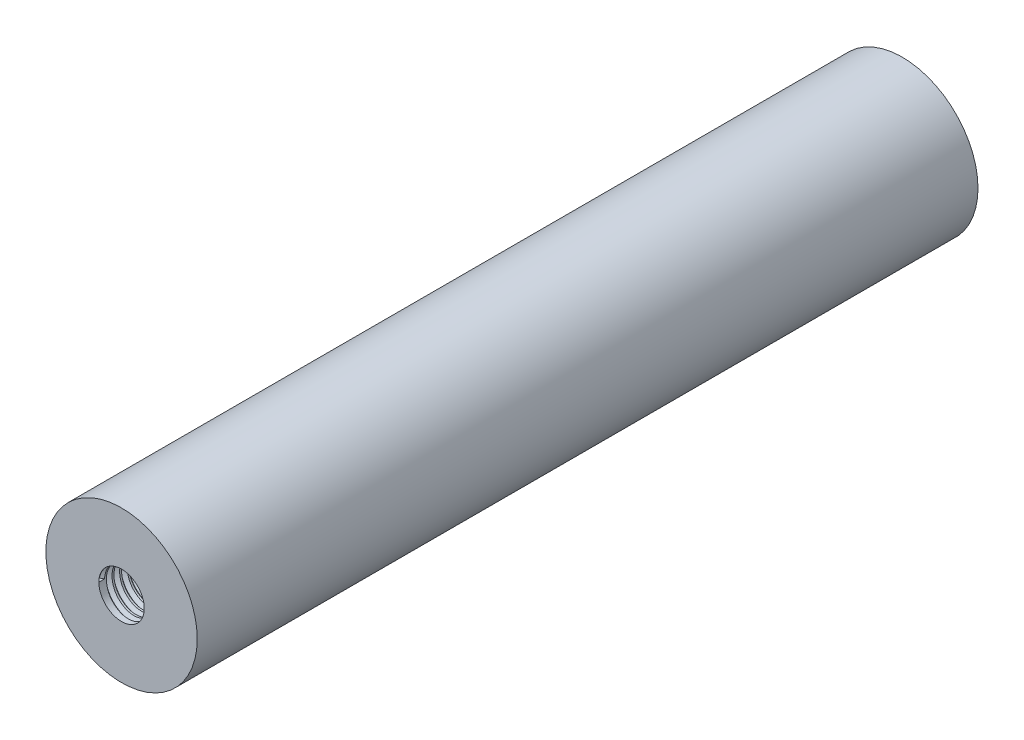
SolidWorks part; units mm, degrees
ref_plane "Front Plane" through (0, 0, 0) normal (0, 0, 1) x (1, 0, 0)
ref_plane "Top Plane" through (0, 0, 0) normal (0, 1, 0) x (1, 0, 0)
ref_plane "Right Plane" through (0, 0, 0) normal (1, 0, 0) x (0, 0, -1)
sketch "Sketch1" plane through (0, 0, 0) normal (0, 0, 1) x (1, 0, 0)
  circle A0 centre (0, 0) radius 10
  dimension "D1" = 20
extrude "Boss-Extrude1" add sketch "Sketch1" along normal mid plane 118.29
sketch "Sketch5" plane through (0, 0, 0) normal (0, 0, 1) x (1, 0, 0)
  line L1 (30.8492, -37.2988) -> (-30.8492, -37.2988)
  line L2 (30.8492, -37.2988) -> (30.8492, 37.2988)
  line L3 (30.8492, 37.2988) -> (-30.8492, 37.2988)
  line L4 (-30.8492, -37.2988) -> (-30.8492, 37.2988)
  line L5 (30.8492, -37.2988) -> (-30.8492, 37.2988) construction
  line L6 (30.8492, 37.2988) -> (-30.8492, -37.2988) construction
  point P0 (0, 0)
extrude "Cut-Extrude2" cut sketch "Sketch5" along normal blind 112 from offset 44
sketch "Sketch6" plane through (0, 0, 44) normal (0, 0, 1) x (1, 0, 0)
  circle A0 centre (0, 0) radius 3
  dimension "D1" = 6
extrude "Cut-Extrude3" cut sketch "Sketch6" against normal blind 10
thread "Thread1" pitch 1 method cut profile "Thread Profile1" start angle 0, offset 0, length 0, pitch 1, diameter 6
ref_plane "Plane1" through (-3, 0, 44) normal (0, -1, 0) x (-1, 0, 0)
sketch "Thread Profile1" plane through (-3, 0, 44) normal (0, -1, 0) x (-1, 0, 0)
  line L0 (0, 0) -> (0, 1) construction
  line L1 (0, 0) -> (0.5413, 0.3125)
  line L2 (0.5413, 0.3125) -> (0.5413, 0.4375)
  line L3 (0.5413, 0.4375) -> (0, 0.75)
  line L4 (0.5413, 0.375) -> (0, 0.375) construction
  line L11 (0, 0) -> (0, 0.75)
  point P2 (0, 0)
  dimension "Pitch" = 1
  dimension "Profile_Angle" = 60
  dimension "Profile_Land" = 0.125
  dimension "Profile_Height" = 0.5413
sketch "Sketch8" plane through (0, 0, -59.145) normal (0, 0, -1) x (-1, 0, 0)
  circle A0 centre (0, 0) radius 3
  dimension "D1" = 6
extrude "Cut-Extrude4" cut sketch "Sketch8" against normal blind 10
thread "Thread2" pitch 1 method cut profile "Thread Profile2" start angle 0, offset 0, length 0, pitch 1, diameter 6
ref_plane "Plane2" through (3, 0, -59.145) normal (0, -1, 0) x (1, 0, 0)
sketch "Thread Profile2" plane through (3, 0, -59.145) normal (0, -1, 0) x (1, 0, 0)
  line L0 (0, 0) -> (0, 1) construction
  line L1 (0, 0) -> (0.5413, 0.3125)
  line L2 (0.5413, 0.3125) -> (0.5413, 0.4375)
  line L3 (0.5413, 0.4375) -> (0, 0.75)
  line L4 (0.5413, 0.375) -> (0, 0.375) construction
  line L11 (0, 0) -> (0, 0.75)
  point P2 (0, 0)
  dimension "Pitch" = 1
  dimension "Profile_Angle" = 60
  dimension "Profile_Land" = 0.125
  dimension "Profile_Height" = 0.5413
